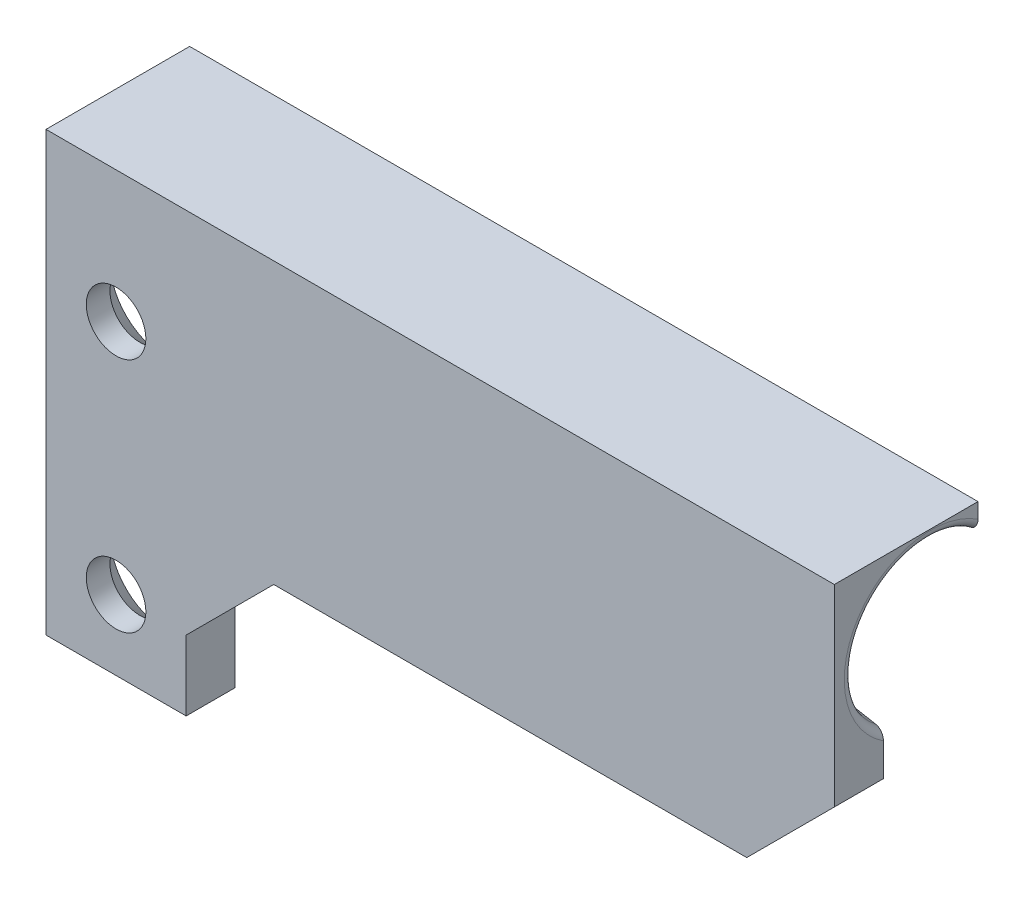
SolidWorks part; units mm, degrees
ref_plane "Front" through (0, 0, 0) normal (0, 0, 1) x (1, 0, 0)
ref_plane "Top" through (0, 0, 0) normal (0, 1, 0) x (1, 0, 0)
ref_plane "Right" through (0, 0, 0) normal (1, 0, 0) x (0, 0, -1)
sketch "Sketch1" plane through (0, 0, 0) normal (0, 0, 1) x (1, 0, 0)
  line L0 (0, 0) -> (0, 25)
  line L1 (0, 25) -> (45, 25)
  line L2 (45, 25) -> (45, 9)
  line L3 (45, 9) -> (8, 9)
  line L4 (8, 9) -> (8, 0)
  line L5 (8, 0) -> (0, 0)
  dimension "D1" = 8
  dimension "D2" = 25
  dimension "D3" = 45
  dimension "D4" = 37
  dimension "D5" = 9
extrude "Boss-Extrude1" add sketch "Sketch1" along normal blind 2.8
sketch "Sketch2" plane through (45, 0, 0) normal (1, 0, 0) x (0, 0, -1)
  line L0 (-2.8, 25) -> (0, 25) construction
  line L1 (0, 9) -> (0, 25) construction
  line L2 (-5.5, 25) -> (-2.8, 25)
  line L3 (-2.8, 25) -> (-2.8, 17.431)
  line L4 (-2.8, 9) -> (-5.1, 9)
  line L5 (-2.8, 9) -> (-2.8, 17.431)
  line L6 (-2.8, 17.431) -> (-5.1, 17.431) construction
  line L7 (-5.1, 9) -> (-5.1, 17.431)
  line L8 (-5.9, 15.016) -> (-5.9, 9) construction
  line L9 (-5.9, 9) -> (-8.2, 9) construction
  line L10 (-8.2, 9) -> (-8.2, 15.7917) construction
  line L11 (-5.9, 15.016) -> (-5.9, 17.431)
  circle A0 centre (-5.5, 20) radius 2.6 construction
  circle A1 centre (-5.5, 20) radius 5 construction
  arc A2 (-5.5, 25) -> (-8.2, 15.7917) centre (-5.5, 20) ccw
  arc A3 (-5.1, 17.431) -> (-5.9, 17.431) centre (-5.5, 20) ccw
  arc A4 (-5.9, 15.016) -> (-8.2, 15.7917) centre (-5.5, 20) cw
  dimension "D1" = 5
  dimension "D2" = 5.5
  dimension "D3" = 5.2
  dimension "D4" = 0.4
  dimension "D5" = 0.4
sketch "Sketch14" plane through (45, 0, 0) normal (1, 0, 0) x (0, 0, -1)
  line L0 (-2.8, 21.3279) -> (-5.5, 22.8868)
  line L1 (-2.8, 25) -> (-2.8, 17.431) construction
  line L2 (-5.5, 22.8868) -> (-8.2, 21.3279)
  line L3 (-8.2, 21.3279) -> (-8.2, 25)
  line L4 (-8.2, 25) -> (-2.8, 25)
  line L5 (-2.8, 25) -> (-2.8, 21.3279)
  circle A0 centre (-5.5, 20) radius 2.5 construction
  dimension "D1" = 5
  dimension "D2" = 120
extrude "Boss-Extrude3" add sketch "Sketch14" against normal up to surface (45 mm away) up to face at (0, 12.5, 1.4)
sketch "Sketch12" plane through (45, 0, 0) normal (1, 0, 0) x (0, 0, -1)
  circle A0 centre (-5.5, 20) radius 5
curve "Helix/Spiral1"
sketch "Sketch13" plane through (45, 0, 0) normal (1, 0, 0) x (0, 0, -1)
  line L0 (-5.5, 16.5) -> (-5.5, 15)
  line L1 (-5.5, 15) -> (-11.5, 15)
  line L2 (-11.5, 15) -> (-11.5, 25)
  line L3 (-11.5, 25) -> (-5.5, 25)
  spline S0 degree 3 poles (-1526.3814, -1268.0197) (113.9625, -79.5513) (11.7533, 34.6702) (-7.8997, 24.1474) (-8.3865, 23.7427) (-9.1543, 22.7981) (-9.4352, 22.2587) (-9.7643, 21.1376) (-9.8125, 20.5563) (-9.6875, 19.4437) (-9.5145, 18.9127) (-8.992, 17.978) (-8.6429, 17.5744) (-7.8372, 16.9455) (-7.381, 16.7202) (10.9686, 11.7614) (48.0505, 149.2076) (-2002.7588, 41.0487) knots -4.151905 -4.151905 -4.151905 -4.151905 0.125 0.125 0.25 0.25 0.375 0.375 0.5 0.5 0.625 0.625 0.75 0.75 0.875 0.875 5.631585 5.631585 5.631585 5.631585 only from (-5.5, 25) to (-5.5, 16.5) construction
  spline S1 degree 3 poles (-5.5, 25) (-6.1545, 24.9375) (-6.7836, 24.745) (-7.8997, 24.1474) (-8.3865, 23.7427) (-9.1543, 22.7981) (-9.4352, 22.2587) (-9.7643, 21.1376) (-9.8125, 20.5563) (-9.6875, 19.4437) (-9.5145, 18.9127) (-8.992, 17.978) (-8.6429, 17.5744) (-7.8372, 16.9455) (-7.381, 16.7202) (-6.4413, 16.4662) (-5.9581, 16.4375) (-5.5, 16.5) knots 0 0 0 0 0.125 0.125 0.25 0.25 0.375 0.375 0.5 0.5 0.625 0.625 0.75 0.75 0.875 0.875 1 1 1 1
  dimension "D1" = 1.5
  dimension "D2" = 6
ref_plane "Plane1" through (0, 0, 5.5) normal (0, 0, -1) x (-1, 0, 0)
chamfer "Chamfer3" distance 1 angle 85 2 edges at (45, 22.1073, 4.15) (45, 22.1073, 6.85) first distance on face at (45, 19.0775, 3.9286)
fillet "Fillet11" radius 1.4 2 edges at (16.785, 22.8868, 5.5) (39.285, 23.4641, 5.5)
sketch "Sketch3" plane through (0, 0, 5.5) normal (0, 0, -1) x (-1, 0, 0)
  line L0 (-45, 20) -> (-31, 20) construction
  line L1 (-31, 20) -> (-31, 22.5)
  line L2 (-31, 22.5) -> (-45, 24.5)
  line L3 (-45, 25) -> (-45, 15.7917) construction
  line L4 (-45, 24.5) -> (-45, 20)
  line L5 (-45, 20) -> (-31, 20)
  dimension "D1" = 4.5
  dimension "D2" = 2.5
  dimension "D3" = 14
revolve "Cut-Revolve1" cut sketch "Sketch3" angle 360 about L0
ref_plane "Plane4" through (0, 0, 5.5) normal (0, 0, 1) x (1, 0, 0)
sketch "Sketch15" plane through (0, 0, 5.5) normal (0, 0, 1) x (1, 0, 0)
  line L0 (45, 20) -> (0, 20) construction
  line L1 (0, 21.3279) -> (0, 0) construction
  line L3 (45, 22.5) -> (0, 22.5)
  line L4 (45, 22.5) -> (45, 17.5)
  line L5 (45, 17.5) -> (0, 17.5)
  line L6 (0, 22.5) -> (0, 17.5)
  line L7 (45, 22.5) -> (0, 17.5) construction
  line L8 (45, 17.5) -> (0, 22.5) construction
  point P6 (22.5, 20)
  dimension "D1" = 5
chamfer "Chamfer2" distance 5 angle 45 2 edges at (45, 9, 1.4) (8, 9, 1.4)
sketch "Sketch5" plane through (0, 0, 2.8) normal (0, 0, 1) x (1, 0, 0)
  line L0 (4, 0) -> (4, 4) construction
  line L1 (0, 0) -> (8, 0) construction
  line L2 (4, 17.5) -> (4, 4) construction
  circle A0 centre (4, 4) radius 1.6
  circle A1 centre (4, 17.5) radius 1.6
  dimension "D1" = 4
  dimension "D2" = 3.2
  dimension "D3" = 17.5
extrude "Cut-Extrude1" cut sketch "Sketch5" against normal through all
fillet "Fillet8" radius 0.3 4 edges at (34.3058, 21.4022, 8.2) (34.3058, 21.4022, 2.8) (16.785, 21.3279, 2.8) (16.785, 21.3279, 8.2)
sketch "Sketch16" plane through (0, 0, 2.8) normal (0, 0, 1) x (1, 0, 0)
  line L0 (31.5, 20) -> (31.5, 13.2) construction
  line L3 (45, 20) -> (0, 20) construction
  line L4 (22.5, 20) -> (22.5, 17.5) construction
  line L5 (45, 17.5) -> (0, 17.5) construction
  circle A0 centre (31.5, 13.2) radius 2.15
  circle A1 centre (31.5, 13.2) radius 4.5 construction
  circle A2 centre (13.5, 13.2) radius 4.5 construction
  circle A3 centre (13.5, 13.2) radius 2.15
  dimension "D2" = 4.3
  dimension "D4" = 9
  dimension "D1" = 9
  dimension "D3" = 6.8
ref_plane "Plane3" through (0, 0, 0) normal (0, 0, -1) x (-1, 0, 0)
ref_plane "Plane5" through (31.5, 0, 0) normal (-1, 0, 0) x (0, 0, 1)
sketch "Sketch17" plane through (31.5, 0, 0) normal (-1, 0, 0) x (0, 0, 1)
  line L0 (2.8, 13.2) -> (7.8, 13.2) construction
  line L1 (2.8, 16.7) -> (4.0858, 16.7)
  line L2 (2.8, 11.05) -> (2.8, 15.35) construction
  line L3 (4.0858, 16.7) -> (4.7929, 15.9929)
  line L4 (6.2071, 15.9929) -> (6.9142, 16.7)
  line L5 (6.9142, 16.7) -> (7.8, 16.7)
  line L6 (7.8, 16.7) -> (7.8, 13.2)
  line L7 (5.5, 15.7) -> (8.862, 15.7) construction
  line L8 (5.5, 16.7) -> (5.5, 20) construction
  line L9 (2.8, 16.7) -> (2.8, 13.2)
  line L10 (2.8, 13.2) -> (7.8, 13.2)
  arc A0 (4.7929, 15.9929) -> (6.2071, 15.9929) centre (5.5, 16.7) ccw
  circle A1 centre (5.5, 16.7) radius 1 construction
  circle A2 centre (5.5, 20) radius 2.3 construction
  dimension "D3" = 1
  dimension "D4" = 7
  dimension "D2" = 2.5
  dimension "D6" = 4.6
  dimension "D1" = 5
  dimension "D5" = 90
revolve "Revolve1" add sketch "Sketch17" angle 360 about L10
fillet "Fillet9" radius 0.5 2 edges at (28, 13.2, 7.8) (28, 13.2, 2.8)
pattern_linear "LPattern2" count 2 spacing 18 along (-1, 0, 0) of "Fillet9", "Revolve1"
hole_wizard "CSK for M3 Flat Head Machine Screw1" positions "Sketch18" profile "Sketch19" countersink size "M3" standard "ANSI Metric" end condition up to next
sketch "Sketch18" plane through (0, 0, 2.8) normal (0, 0, 1) x (1, 0, 0)
  point P0 (4, 17.5)
  point P3 (4, 4)
sketch "Sketch19" plane through (4, 17.5, 2.8) normal (1, 0, 0) x (0, -1, 0)
  line L0 (0, 0) -> (0, 2.8)
  line L1 (0, 2.8) -> (1.7, 2.8)
  line L2 (1.7, 2.8) -> (1.7, 1.45)
  line L3 (1.7, 1.45) -> (3.15, 0)
  line L5 (3.15, 0) -> (0, 0)
  line L6 (-1.7, 1.45) -> (-3.15, 0) construction
  line L11 (0, -6.35) -> (0, 107.95) construction
  dimension "Thru Hole Dia." = 3.4
  dimension "Thru Hole Depth" = 2.8
  dimension "Near C'Sink Dia." = 6.3
  dimension "Near C'Sink Angle" = 90
sketch "Sketch21" [suppressed] plane through (0, 0, 0) normal (0, 0, -1) x (-1, 0, 0)
  line L0 (0, 25) -> (0, 55)
  line L1 (0, 55) -> (-8, 55)
  line L2 (-8, 55) -> (-8, 49)
  line L3 (-8, 49) -> (-45, 25)
  line L4 (0, 25) -> (-45, 25) construction
  line L5 (-45, 25) -> (0, 25)
  line L6 (0, 0) -> (-8, 0) construction
  dimension "D1" = 55
  dimension "D2" = 6
extrude "Boss-Extrude4" [suppressed] add sketch "Sketch21" against normal up to surface (2.8 mm away)
hole_wizard "CSK for M3 Flat Head Machine Screw2" [suppressed] positions "Sketch23" profile "Sketch24" countersink size "M3" standard "ANSI Metric"
sketch "Sketch23" plane through (0, 0, 2.8) normal (0, 0, 1) x (1, 0, 0)
  line L0 (4, 55) -> (4, 51) construction
  line L1 (8, 55) -> (0, 55) construction
  line L2 (4, 51) -> (4, 37.5) construction
  circle A0 centre (4, 17.5) radius 1.7 construction
  point P0 (4, 51)
  point P2 (4, 37.5)
  dimension "D1" = 20
  dimension "D2" = 13.5
sketch "Sketch24" plane through (4, 51, 2.8) normal (1, 0, 0) x (0, -1, 0)
  line L0 (0, 0) -> (0, 3.7604)
  line L1 (0, 3.7604) -> (1.6, 2.799)
  line L2 (1.6, 2.799) -> (1.6, 1.55)
  line L3 (1.6, 1.55) -> (3.15, 0)
  line L5 (3.15, 0) -> (0, 0)
  line L6 (-1.6, 1.55) -> (-3.15, 0) construction
  line L10 (0, 3.7604) -> (-1.6, 2.799) construction
  line L11 (0, -6.35) -> (0, 107.95) construction
  dimension "Hole Dia." = 3.2
  dimension "Hole Depth" = 2.799
  dimension "Near C'Sink Dia." = 6.3
  dimension "Near C'Sink Angle" = 90
  dimension "Drill Angle" = 118
fillet "Fillet10" [suppressed] radius 0.5
fillet "Fillet12" [suppressed] radius 0.5
chamfer "Chamfer4" [suppressed] distance 5.5 angle 60
fillet "Fillet13" radius 0.5 1 edges at (45, 22.7, 1.9)
fillet "Fillet14" [suppressed] radius 4
mirror "Mirror1" about plane through (0, 0, 0) normal (0, 0, -1) of bodies 119 115
delete or keep bodies "Body-Delete/Keep 1" type keep bodies bodies 116
